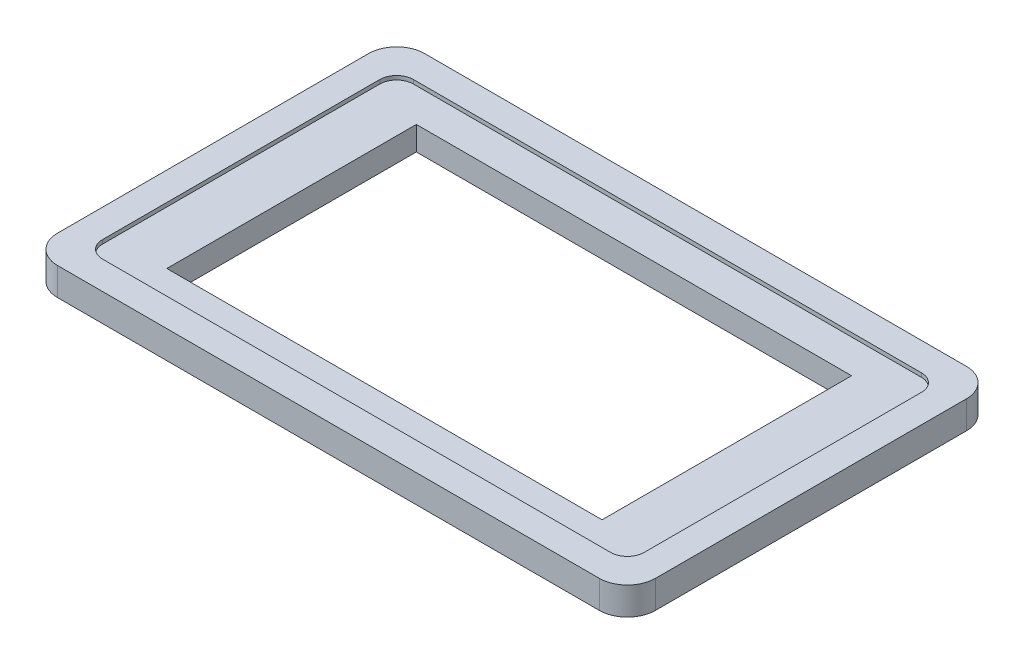
SolidWorks part; units mm, degrees
ref_plane "Front Plane" through (0, 0, 0) normal (0, 0, 1) x (1, 0, 0)
ref_plane "  Top Plane" through (0, 0, 0) normal (0, 1, 0) x (1, 0, 0)
ref_plane "Right Plane" through (0, 0, 0) normal (1, 0, 0) x (0, 0, -1)
sketch "Front Face" plane through (0, 0, 0) normal (0, 1, 0) x (1, 0, 0)
  line L0 (106.48, 120.76) -> (106.48, 10) construction
  line L1 (10, 0) -> (202.96, 0)
  line L2 (0, 10) -> (0, 120.76)
  line L3 (10, 130.76) -> (202.96, 130.76)
  line L4 (212.96, 10) -> (212.96, 120.76)
  line L5 (16, 10) -> (196.96, 10)
  line L6 (10, 16) -> (10, 114.76)
  line L7 (16, 120.76) -> (196.96, 120.76)
  line L8 (202.96, 16) -> (202.96, 114.76)
  line L9 (28.965, 108.815) -> (183.995, 108.815)
  line L10 (28.965, 108.815) -> (28.965, 21.945)
  line L11 (28.965, 21.945) -> (183.995, 21.945) construction
  line L12 (183.995, 108.815) -> (183.995, 21.945)
  line L13 (10, 65.38) -> (202.96, 65.38) construction
  line L19 (28.965, 21.945) -> (183.995, 21.945) construction
  line L20 (28.965, 21.945) -> (28.965, 19.945)
  line L21 (28.965, 19.945) -> (183.995, 19.945)
  line L22 (183.995, 21.945) -> (183.995, 19.945)
  arc A0 (196.96, 120.76) -> (202.96, 114.76) centre (196.96, 114.76) cw
  arc A1 (196.96, 10) -> (202.96, 16) centre (196.96, 16) ccw
  arc A2 (16, 10) -> (10, 16) centre (16, 16) cw
  arc A3 (10, 114.76) -> (16, 120.76) centre (16, 114.76) cw
  arc A4 (202.96, 130.76) -> (212.96, 120.76) centre (202.96, 120.76) cw
  arc A5 (202.96, 0) -> (212.96, 10) centre (202.96, 10) ccw
  arc A6 (10, 0) -> (0, 10) centre (10, 10) cw
  arc A7 (0, 120.76) -> (10, 130.76) centre (10, 120.76) cw
  point P23 (0, 0)
  point P34 (28.965, 65.38)
  point P35 (106.48, 108.815)
  dimension "D7" = 6
  dimension "D8" = 10
  dimension "D1" = 10
  dimension "D2" = 10
  dimension "D3" = 10
  dimension "D4" = 10
  dimension "D5" = 192.96
  dimension "D6" = 110.76
  dimension "D9" = 155.03
  dimension "D10" = 86.87
  dimension "D11" = 2
extrude "Boss-Extrude1" add sketch "Front Face" along normal blind 1.4 contours A7 L2 A6 L1 A5 L4 A4 L3 L6 A3 L7 A0 L8 A1 L5 A2 region at (4.696, 0, -4.696)
extrude "Boss-Extrude2" add sketch "Front Face<3>" against normal blind 8.5 contours A3 L6 A2 L5 A1 L8 A0 L7 L9 L12 L11 L10 | A7 L2 A6 L1 A5 L4 A4 L3 L6 A3 L7 A0 L8 A1 L5 A2 region at (4.696, 0, -4.696) region at (13.3306, 0, -13.3306)
sketch "Front Face<3>" plane through (0, 0, 0) normal (0, 1, 0) x (1, 0, 0) same geometry as "Front Face"
